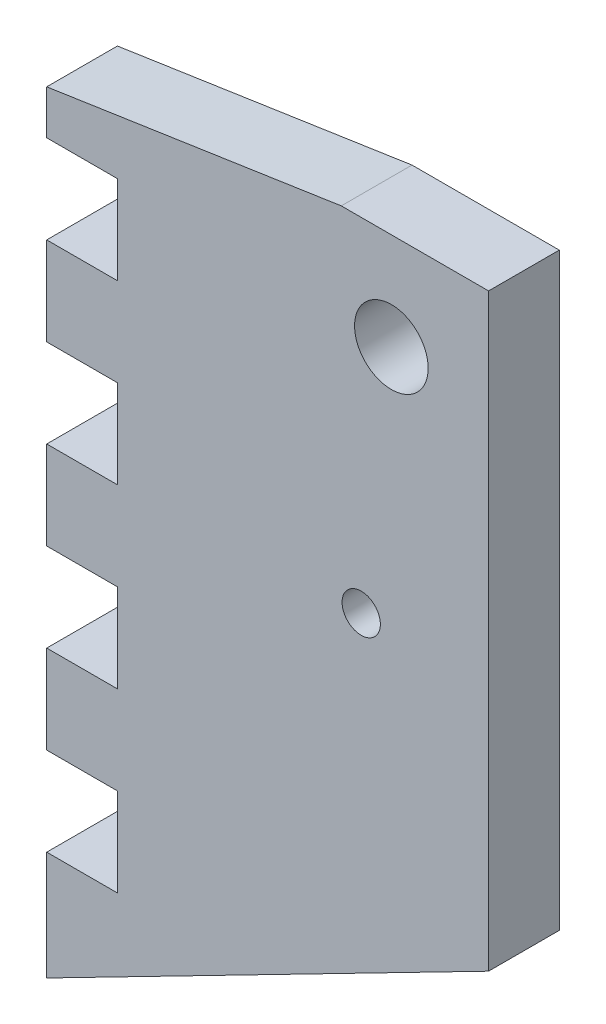
SolidWorks part; units mm, degrees
material "Thornel VCB-20 Carbon Cloth"
ref_plane "Front Plane" through (0, 0, 0) normal (0, 0, 1) x (1, 0, 0)
ref_plane "Top Plane" through (0, 0, 0) normal (0, 1, 0) x (1, 0, 0)
ref_plane "Right Plane" through (0, 0, 0) normal (1, 0, 0) x (0, 0, -1)
sketch "Sketch1" plane through (0, 0, 0) normal (0, 0, 1) x (1, 0, 0)
  line L0 (0, 0) -> (-38.1, 0)
  line L1 (0, 0) -> (0, -50.8)
  line L2 (-38.1, 0) -> (-38.1, -7.62)
  line L3 (-38.1, -7.62) -> (-32.004, -7.62)
  line L4 (-32.004, -7.62) -> (-32.004, -15.24)
  line L5 (-32.004, -15.24) -> (-38.1, -15.24)
  line L6 (-38.1, -45.72) -> (-38.1, -70.358)
  line L7 (-38.1, -15.24) -> (-38.1, -22.86)
  line L8 (-38.1, -22.86) -> (-32.004, -22.86)
  line L9 (-32.004, -22.86) -> (-32.004, -30.48)
  line L10 (-32.004, -30.48) -> (-38.1, -30.48)
  line L11 (-38.1, -30.48) -> (-38.1, -38.1)
  line L12 (-38.1, -38.1) -> (-32.004, -38.1)
  line L13 (-32.004, -38.1) -> (-32.004, -45.72)
  line L14 (-32.004, -45.72) -> (-38.1, -45.72)
  line L15 (-38.1, -70.358) -> (0, -50.8)
  circle A0 centre (-8.382, -8.382) radius 3.175
  dimension "D9" = 6.35
  dimension "D1" = 38.1
  dimension "D2" = 50.8
  dimension "D3" = 7.62
  dimension "D4" = 7.62
  dimension "D6" = 6.096
  dimension "D8" = 70.358
  dimension "D12" = 8.382
  dimension "D13" = 8.382
  dimension "D7" = 3
extrude "Boss-Extrude1" add sketch "Sketch1" along normal blind 6.096 contours L6 L15 L1 L0 L2 L3 L4 L5 L7 L8 L9 L10 L11 L12 L13 L14 A0 region at (-19.2717, -31.1343, 0)
sketch "Sketch2" plane through (0, 0, 0) normal (0, 0, -1) x (-1, 0, 0)
  line L5 (38.1, 0) -> (12.7, 0)
  line L6 (0, 0) -> (38.1, 0) construction
  line L7 (12.7, 0) -> (38.1, -3.81)
  line L8 (38.1, 0) -> (38.1, -7.62) construction
  line L9 (38.1, -3.81) -> (38.1, 0)
  dimension "D1" = 25.4
  dimension "D2" = 3.81
extrude "Cut-Extrude1" cut sketch "Sketch2" against normal blind 8.636
sketch "Sketch4" plane through (0, 0, 6.096) normal (0, 0, 1) x (1, 0, 0)
  line L0 (-38.1, -45.72) -> (-38.1, -53.34)
  line L1 (-38.1, -45.72) -> (-38.1, -70.358) construction
  line L2 (-38.1, -53.34) -> (-32.004, -53.34)
  line L3 (-32.004, -53.34) -> (-32.004, -60.96)
  line L4 (-32.004, -60.96) -> (-38.1, -60.96)
  line L5 (-38.1, -60.96) -> (-38.1, -53.34)
  line M18 (-38.1, -45.72) -> (-38.1, -70.358)
  dimension "D1" = 7.62
  dimension "D2" = 6.096
  dimension "D3" = 6.096
  dimension "D4" = 7.62
extrude "Cut-Extrude2" cut sketch "Sketch4" against normal through all contours L4 L3 L2 M18 region at (-35.052, -57.15, 6.096)
sketch "Sketch5" plane through (0, 0, 0) normal (0, 0, -1) x (-1, 0, 0)
  line L0 (8.382, -8.382) -> (10.9822, -29.559) construction
  line L1 (8.382, -8.382) -> (8.382, -39.2411) construction
  circle A0 centre (8.382, -8.382) radius 3.175 construction
  circle A1 centre (10.9822, -29.559) radius 1.651
  dimension "D1" = 21.336
  dimension "D2" = 7
extrude "Cut-Extrude4" cut sketch "Sketch5" against normal up to surface (6.096 mm away) up to face at (-5.207, -8.382, 6.096)
ref_plane "Plane1" through (0, 0, 0) normal (0, 0, -1) x (-1, 0, 0)
sketch "Sketch7" plane through (0, 0, 0) normal (0, 0, -1) x (-1, 0, 0)
  line L1 (4.8596, -18.6014) -> (8.6696, -18.6014)
  line L2 (4.8596, -18.6014) -> (4.8596, -22.4114)
  line L3 (4.8596, -22.4114) -> (8.6696, -22.4114)
  line L4 (8.6696, -18.6014) -> (8.6696, -22.4114)
  dimension "D1" = 3.81
  dimension "D2" = 3.81
